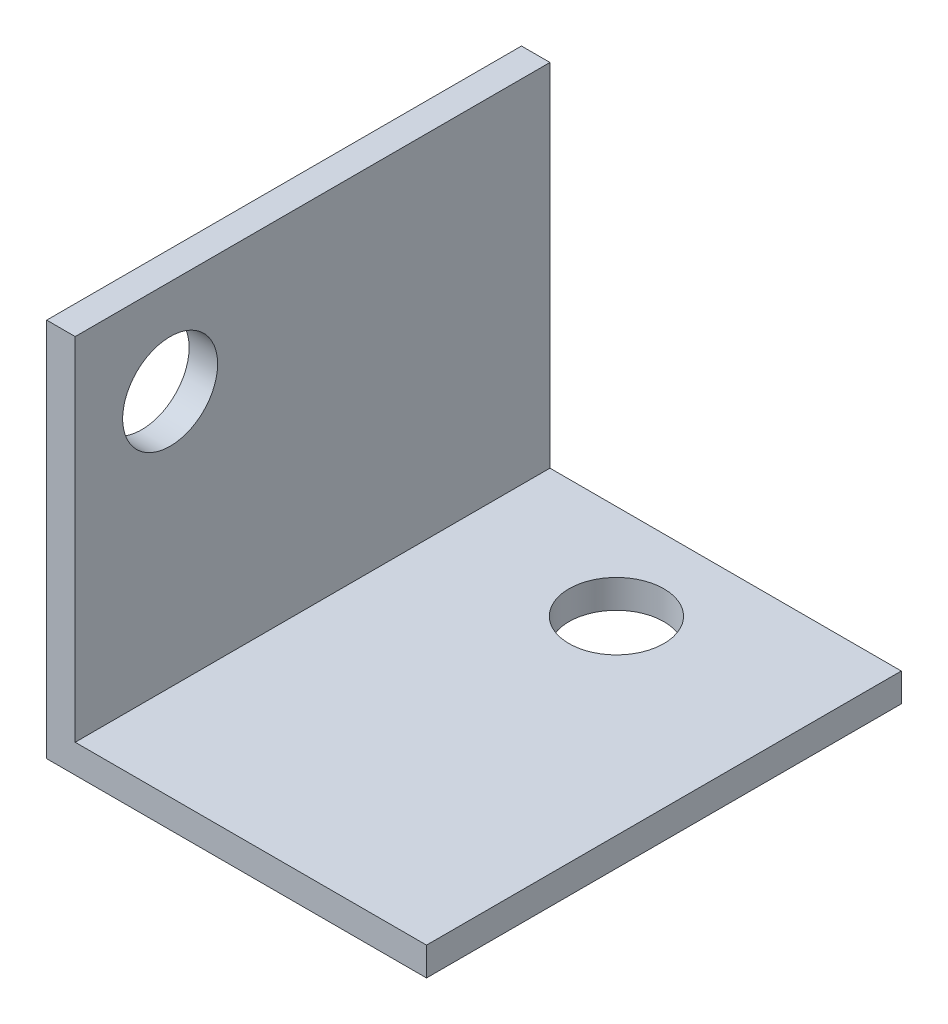
SolidWorks part; units mm, degrees
material "1060 Alloy"
ref_plane "xy" through (0, 0, 0) normal (0, 0, 1) x (1, 0, 0)
ref_plane "xz" through (0, 0, 0) normal (0, 1, 0) x (1, 0, 0)
ref_plane "yz" through (0, 0, 0) normal (1, 0, 0) x (0, 0, -1)
ref_axis "x" through (-88.99, 0, 0) along (1, 0, 0)
ref_axis "y" through (0, 55, 0) along (0, -1, 0)
ref_axis "z" through (0, 0, -88.99) along (0, 0, 1)
sketch "Sketch1" plane through (0, 0, 0) normal (0, 0, 1) x (1, 0, 0)
  line L0 (0, 0) -> (20, 0)
  line L1 (0, 0) -> (0, 20)
  dimension "D1" = 20
extrude "Extrude-Thin1" add sketch "Sketch1" along normal blind 25 thin thin type one direction wall 1.5
sketch "Sketch2" plane through (0, 0, 0) normal (0, -1, 0) x (-1, 0, 0)
  line L0 (-10, 0) -> (-10, -5) construction
  line L1 (-20, 0) -> (0, 0) construction
  circle A0 centre (-10, -5) radius 2.5
  dimension "D2" = 5
  dimension "D1" = 5
extrude "Cut-Extrude1" cut sketch "Sketch2" against normal through all
sketch "Sketch3" plane through (1.5, 0, 0) normal (1, 0, 0) x (0, 0, -1)
  line L0 (-20, 15) -> (-20, 20) construction
  line L1 (-25, 20) -> (0, 20) construction
  line L2 (-20, 15) -> (-25, 15) construction
  line L3 (-25, 1.5) -> (-25, 20) construction
  circle A0 centre (-20, 15) radius 2.5
  dimension "D1" = 5
  dimension "D2" = 5
extrude "Cut-Extrude2" cut sketch "Sketch3" against normal through all
